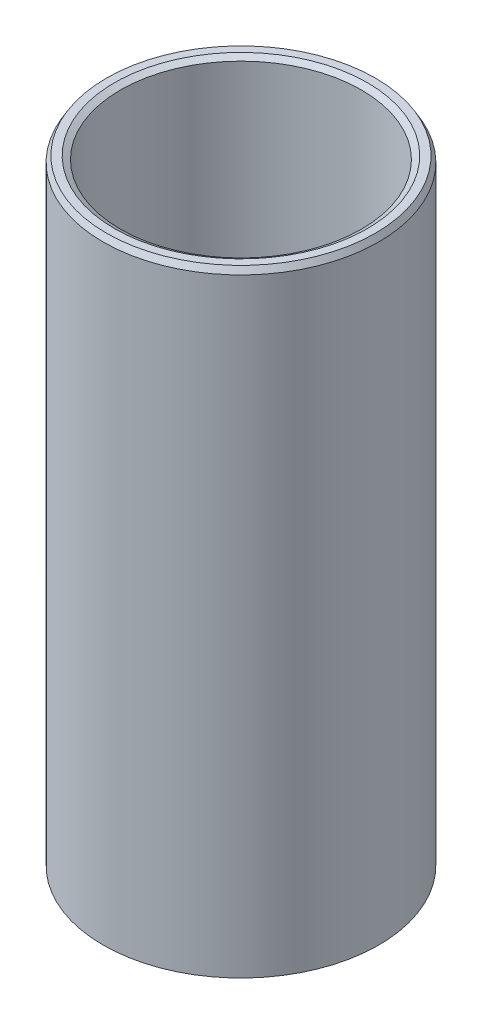
SolidWorks part; units mm, degrees
ref_plane "Front Plane" through (0, 0, 0) normal (0, 0, 1) x (1, 0, 0)
ref_plane "Top Plane" through (0, 0, 0) normal (0, 1, 0) x (1, 0, 0)
ref_plane "Right Plane" through (0, 0, 0) normal (1, 0, 0) x (0, 0, -1)
sketch "Sketch1" plane through (0, 0, 0) normal (0, 1, 0) x (1, 0, 0)
  circle A0 centre (0, 0) radius 30
  dimension "SLEEVE_OD" = 60
extrude "Boss-Extrude1" add sketch "Sketch1" along normal blind 134.5707
sketch "Sketch2" plane through (0, 0, 0) normal (0, 1, 0) x (1, 0, 0)
  circle A0 centre (0, 0) radius 26.2433
  dimension "BORE_D" = 52.4866
extrude "Cut-Extrude1" cut sketch "Sketch2" along normal through all
chamfer "Chamfer1" distance 1.2799 angle 30 4 edges at (0, 134.5707, 26.2433) (0, 0, 26.2433) (0, 0, 30) (0, 134.5707, 30) first distance on face at (0, 134.5707, 26.2433) first distance on face at (0, 0, 26.2433) first distance on face at (0, 134.5707, 30)
